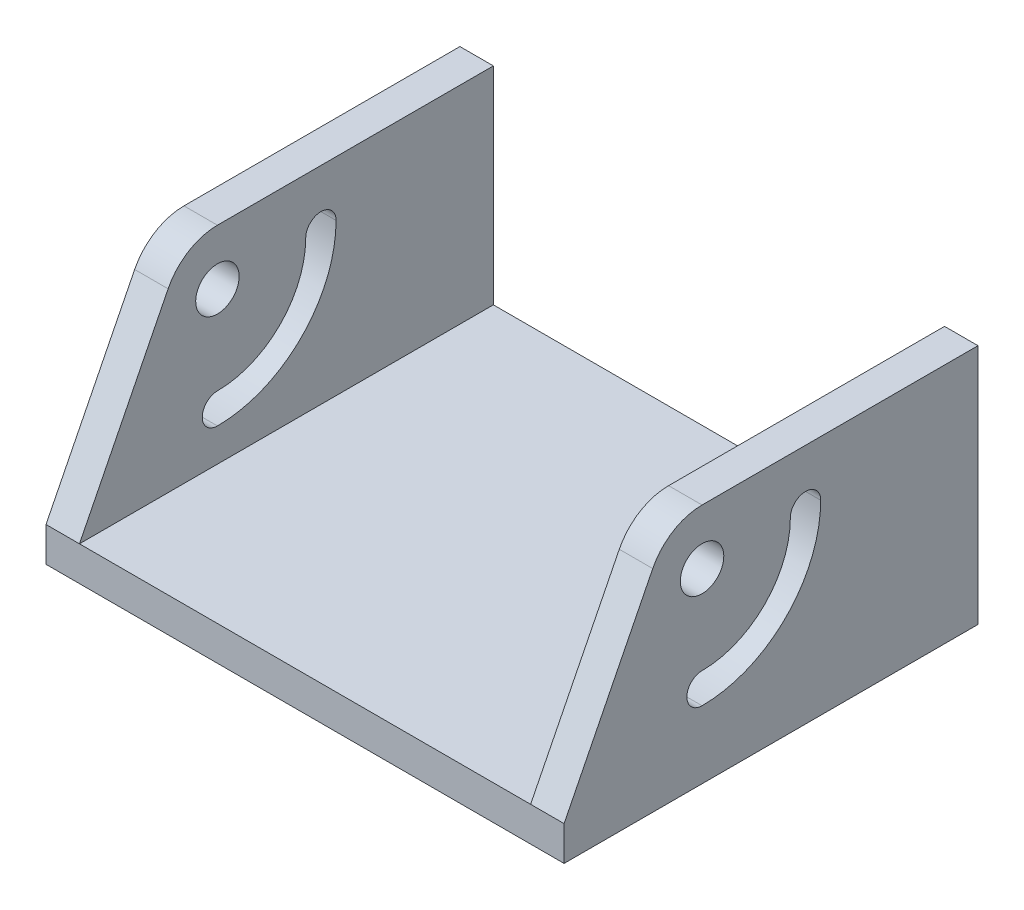
SolidWorks part; units mm, degrees
ref_plane "前视基准面" through (0, 0, 0) normal (0, 0, 1) x (1, 0, 0)
ref_plane "上视基准面" through (0, 0, 0) normal (0, 1, 0) x (1, 0, 0)
ref_plane "右视基准面" through (0, 0, 0) normal (1, 0, 0) x (0, 0, -1)
sketch "草图1" plane through (0, 0, 0) normal (0, 0, 1) x (1, 0, 0)
  line L0 (-37.55, 0) -> (37.55, 0)
  line L1 (37.55, 0) -> (37.55, 35)
  line L2 (37.55, 35) -> (32.7, 35)
  line L3 (32.7, 35) -> (32.7, 5)
  line L4 (32.7, 5) -> (-32.7, 5)
  line L5 (-32.7, 5) -> (-32.7, 35)
  line L6 (-32.7, 35) -> (-37.55, 35)
  line L7 (-37.55, 35) -> (-37.55, 0)
  point P7 (0, 0)
  dimension "D1" = 5
  dimension "D2" = 4.85
  dimension "D3" = 65.4
  dimension "D4" = 30
extrude "凸台-拉伸1" add sketch "草图1" along normal blind 30 and the other way blind 30
sketch "草图3" plane through (-37.55, 0, 0) normal (-1, 0, 0) x (0, 0, 1)
  line L1 (30, 5) -> (17.1492, 30.5902)
  line L2 (-30, 35) -> (30, 35) construction
  line L5 (30, 35) -> (30, 5)
  line L6 (10, 35) -> (10, 0) construction
  line L7 (-30, 0) -> (30, 0) construction
  line L8 (10, 35) -> (30, 35)
  circle A7 centre (10, 27) radius 3.15
  arc A8 (-2.8, 27) -> (10, 14.2) centre (10, 27) ccw
  arc A9 (-7.2, 27) -> (10, 9.8) centre (10, 27) ccw
  arc A10 (-2.8, 27) -> (-7.2, 27) centre (-5, 27) ccw
  arc A11 (10, 14.2) -> (10, 9.8) centre (10, 12) cw
  arc A12 (10, 35) -> (17.1492, 30.5902) centre (10, 27) cw
  line M15 (30, 0) -> (30, 35)
  line M16 (30, 35) -> (-30, 35)
  dimension "D1" = 6.3
  dimension "D2" = 8
  dimension "D3" = 15
  dimension "D5" = 20
  dimension "D4" = 4.4
  dimension "D6" = 90
extrude "切除-拉伸1" cut sketch "草图3" against normal through all contours L1 M16 M15 | L6 A7 | A7 L6 | L6 A8 A10 A9 | A11 L6 region at (-37.55, 12, 10.9337) region at (-37.55, 18.1031, 0.0145) region at (-37.55, 27, 11.3369) region at (-37.55, 27, 8.6631) region at (-37.55, 25.1618, 24.7888)
